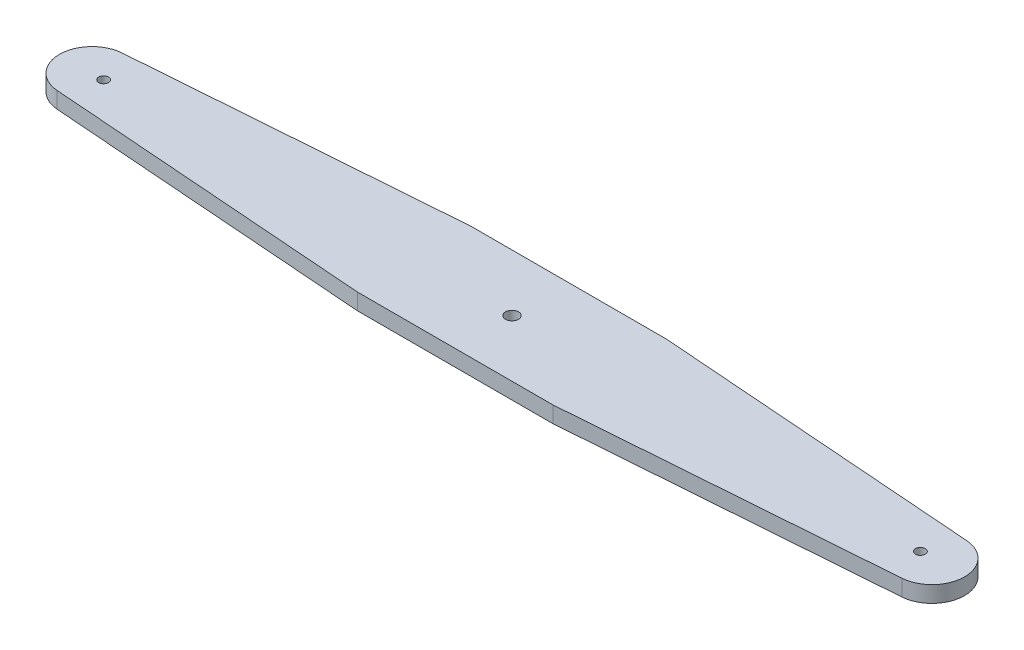
SolidWorks part; units mm, degrees
ref_plane "Front Plane" through (0, 0, 0) normal (0, 0, 1) x (1, 0, 0)
ref_plane "Top Plane" through (0, 0, 0) normal (0, 1, 0) x (1, 0, 0)
ref_plane "Right Plane" through (0, 0, 0) normal (1, 0, 0) x (0, 0, -1)
sketch "Sketch1" plane through (0, 0, 0) normal (0, 1, 0) x (1, 0, 0)
  line L0 (7.4021, -69.9094) -> (127.4021, -69.9094)
  line L1 (127.4021, -69.9094) -> (326.8402, -84.8906)
  line L2 (7.4021, -69.9094) -> (-192.036, -84.8906)
  line L3 (-192.036, -124.7782) -> (7.4021, -139.7594)
  line L4 (7.4021, -139.7594) -> (127.4021, -139.7594)
  line L5 (127.4021, -139.7594) -> (326.8402, -124.7782)
  line L7 (-183.4229, -104.8344) -> (318.2271, -104.8344) construction
  line L8 (67.4021, -69.9094) -> (67.4021, -139.7594) construction
  circle A0 centre (-183.4229, -104.8344) radius 3
  circle A1 centre (318.2271, -104.8344) radius 3
  arc A2 (-192.036, -84.8906) -> (-192.036, -124.7782) centre (-190.5379, -104.8344) ccw
  arc A3 (326.8402, -84.8906) -> (326.8402, -124.7782) centre (325.3421, -104.8344) cw
  circle A4 centre (67.4021, -104.8344) radius 4
  point P15 (67.4021, -104.8344)
  point P16 (67.4021, -104.8344)
  dimension "D2" = 6
  dimension "D3" = 6
  dimension "D11" = 20
  dimension "D12" = 20
  dimension "D13" = 8
  dimension "D1" = 501.65
  dimension "D4" = 120
  dimension "D5" = 120
  dimension "D6" = 200
  dimension "D7" = 200
  dimension "D8" = 200
  dimension "D9" = 200
  dimension "D10" = 69.85
extrude "Boss-Extrude1" add sketch "Sketch1" along normal blind 10
equation "\"D5@Sketch1\"=\"D4@Sketch1\""
equation "\"D8@Sketch1\"=\"D7@Sketch1\""
equation "\"D9@Sketch1\"=\"D7@Sketch1\""
equation "\"D6@Sketch1\"=\"D7@Sketch1\""
equation "\"D12@Sketch1\"=\"D11@Sketch1\""
